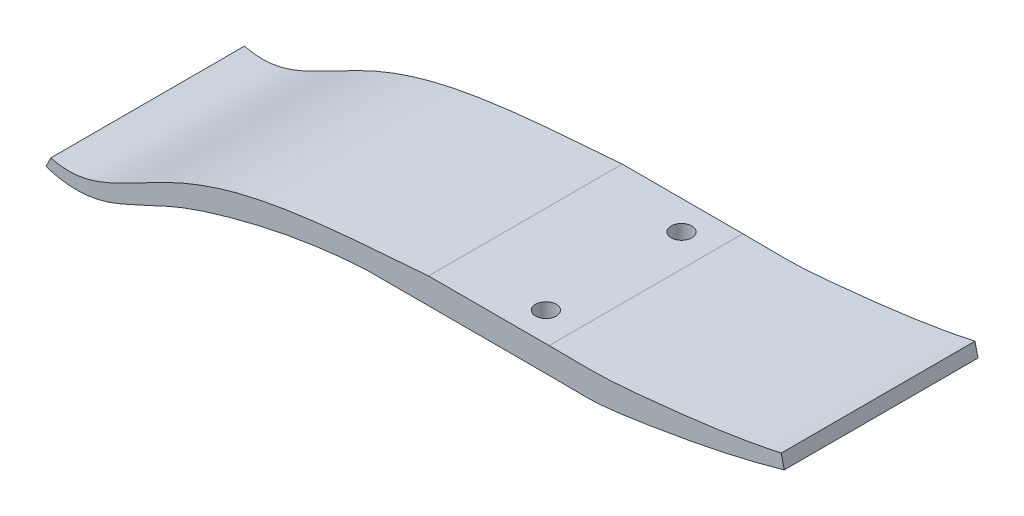
SolidWorks part; units mm, degrees
ref_plane "Piano frontale" through (0, 0, 0) normal (0, 0, 1) x (1, 0, 0)
ref_plane "Piano superiore" through (0, 0, 0) normal (0, 1, 0) x (1, 0, 0)
ref_plane "Piano destro" through (0, 0, 0) normal (1, 0, 0) x (0, 0, -1)
sketch "Schizzo1" plane through (0, 0, 0) normal (0, 0, 1) x (1, 0, 0)
  line L0 (0, 0) -> (150, 0)
  line L1 (-321.1596, 15.9937) -> (-560.6113, 796.7672) construction
  line L2 (-4.3491, -26.8408) -> (-3.9663, -26.937)
  line L3 (-51.9474, 387.4316) -> (764.7193, 387.4316) construction
  line L4 (-5.8196, -29.8434) -> (-4.3491, -26.8408)
  line L5 (221.8951, 7.1301) -> (222.8247, 3.0623)
  line L6 (93.1769, -8) -> (150, -8)
  spline S0 degree 3 poles (112.6528, 0) (98.2377, -1.1782) (76.3254, -2.3671) (50.3861, -7.7153) (33.0349, -14.2602) (16.9038, -23.444) (3.8284, -28.9701) (-4.3491, -26.8408) knots 0 0 0 0 0.357718 0.541412 0.651992 0.814468 1 1 1 1
  spline S1 degree 3 poles (93.1769, -8) (78.0958, -8.807) (58.5152, -12.4651) (33.4259, -20.4928) (21.8686, -26.5918) (8.4687, -31.8499) (-0.0208, -31.918) (-5.8196, -29.8434) knots 0 0 0 0 0.439768 0.579666 0.76758 0.820027 1 1 1 1
  spline S2 degree 3 poles (150, 0) (155.1864, -0.0719) (162.776, -0.1927) (171.9425, 0.1981) (191.0542, 2.0423) (208.371, 4.1609) (221.8951, 7.1301) knots 0 0 0 0 0.180513 0.221559 0.410457 1 1 1 1
  spline S3 degree 3 poles (150, -8) (160.9347, -8.1785) (167.7326, -7.9814) (191.2182, -4.4007) (208.8639, -0.958) (222.8247, 3.0623) knots 0 0 0 0 0.132806 0.367169 1 1 1 1
  dimension "D1" = 150
  dimension "D2" = 231
extrude "Estrusione-Estrusione1" add sketch "Schizzo1" against normal blind 60 contours L6 S3 L5 S2 L0 S0 L4 S1 region at (111.6729, -7.4603, 0)
sketch "Schizzo2" plane through (0, 0, 0) normal (0, 1, 0) x (1, 0, 0)
  line L0 (140, 65.3766) -> (140, -9.0702) construction
  line L1 (131.5646, 51) -> (144.2572, 51) construction
  line L2 (112.6528, 30) -> (150, 30) construction
  line L3 (112.6528, 60) -> (112.6528, 0) construction
  line L4 (150, 60) -> (150, 0) construction
  line L5 (112.6528, 60) -> (150, 60) construction
  circle A0 centre (140, 51) radius 3.2
  circle A1 centre (140, 9) radius 3.2
  dimension "D3" = 6.4
  dimension "D1" = 10
  dimension "D2" = 9
extrude "Taglio-Estrusione1" cut sketch "Schizzo2" against normal through all
